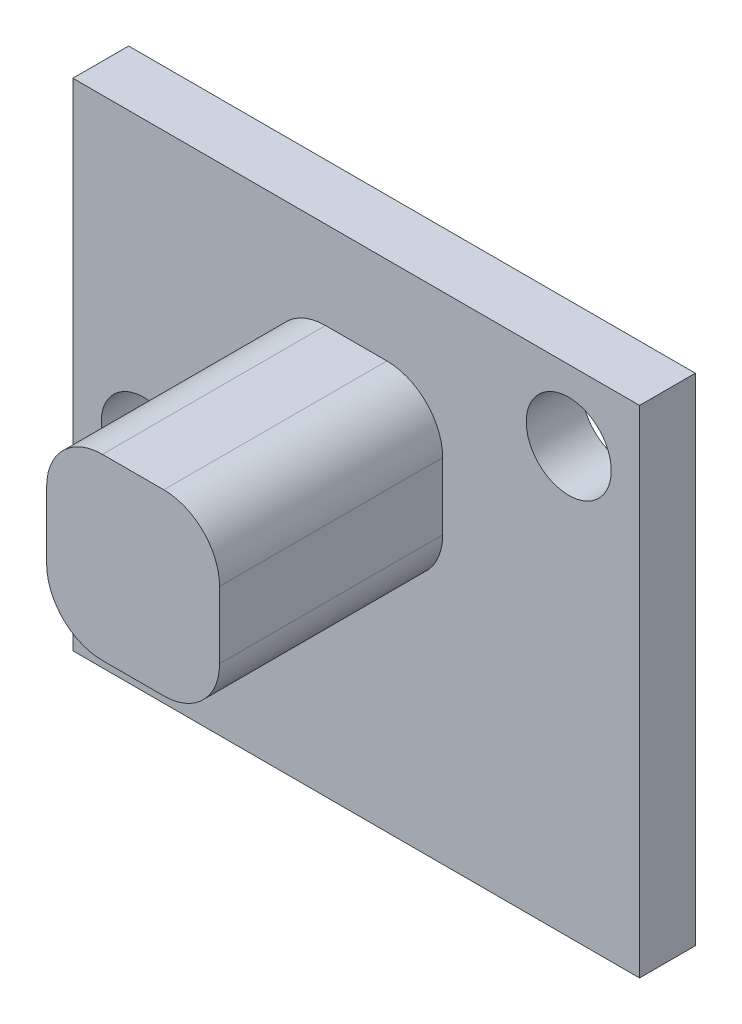
SolidWorks part; units mm, degrees
note: The reader was unsure of these and kept them because the rebuilt part matched: shared geometry of "Model<3>".
ref_plane "Front Plane" through (0, 0, 0) normal (0, 0, 1) x (1, 0, 0)
ref_plane "Top Plane" through (0, 0, 0) normal (0, 1, 0) x (1, 0, 0)
ref_plane "Right Plane" through (0, 0, 0) normal (1, 0, 0) x (0, 0, -1)
sketch "Model" plane through (0, 0, 0) normal (0, 0, 1) x (1, 0, 0)
  line L0 (0, 0) -> (20.32, 0)
  line L1 (20.32, 17.78) -> (0, 17.78)
  line L2 (0, 17.78) -> (0, 0)
  line L3 (20.32, 0) -> (20.32, 17.78)
  line L4 (7.06, 8.23) -> (13.26, 8.23)
  line L5 (7.06, 14.63) -> (13.26, 14.63)
  line L595 (13.26, 14.63) -> (13.26, 8.23)
  line L596 (7.06, 8.23) -> (7.06, 14.63)
  circle A0 centre (2.54, 7.62) radius 1.524
  circle A1 centre (17.78, 15.24) radius 1.524
extrude "Boss-Extrude1" add sketch "Model" along normal blind 2 contours L596 L4 L595 L5 | L0 L3 L1 L2 A1 A0 L4 L596 L5 L595
extrude "Boss-Extrude2" add sketch "Model<3>" along normal blind 10 contours L596 L4 L595 L5
sketch "Model<3>" plane through (0, 0, 0) normal (0, 0, 1) x (1, 0, 0) same geometry as "Model"
fillet "Fillet1" radius 2 4 edges at (7.06, 14.63, 6) (7.06, 8.23, 6) (13.26, 8.23, 6) (13.26, 14.63, 6)
